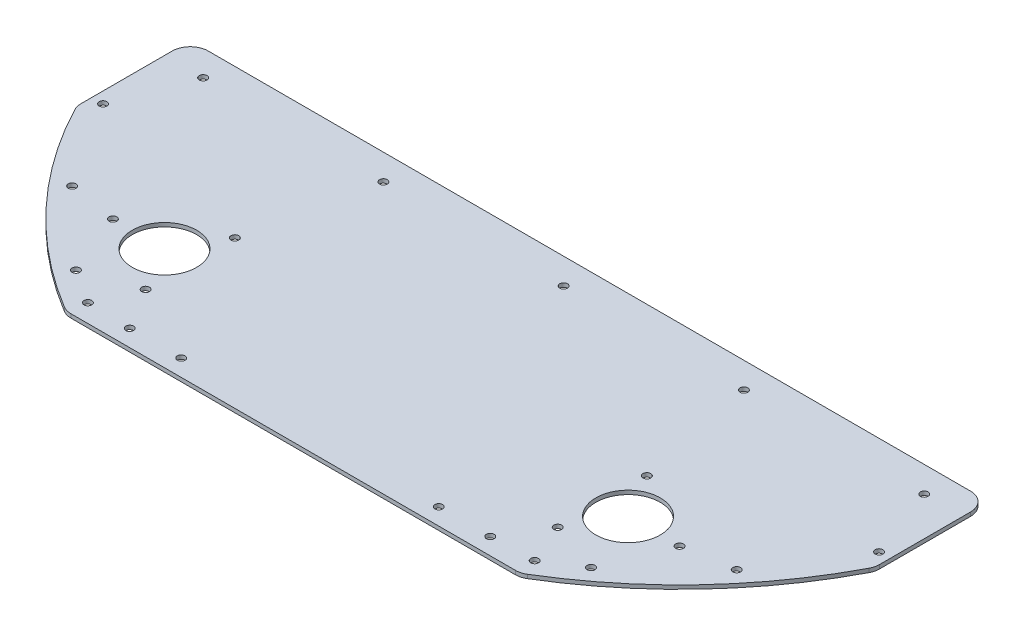
SolidWorks part; units mm, degrees
material "3.3535 (EN-AW 5754)"
ref_plane "Plan de face" through (0, 0, 0) normal (0, 0, 1) x (1, 0, 0)
ref_plane "Plan de dessus" through (0, 0, 0) normal (0, 1, 0) x (1, 0, 0)
ref_plane "Plan de droite" through (0, 0, 0) normal (1, 0, 0) x (0, 0, -1)
sketch "Esquisse1" plane through (0, 0, 0) normal (0, 1, 0) x (1, 0, 0)
  line L0 (0, 0) -> (0, -150) construction
  line L1 (-155, -35) -> (155, -35)
  line L2 (-155, -35) -> (-155, -79.0633)
  line L3 (-88.1816, -150) -> (88.1816, -150)
  line L6 (155, -35) -> (155, -79.0633)
  line L8 (110, -110) -> (90, -110) construction
  circle A0 centre (-70, -45) radius 1.5
  circle A1 centre (0, -45) radius 1.5
  circle A2 centre (90, -110) radius 12.5
  circle A3 centre (80, -127.3205) radius 1.5
  circle A4 centre (110, -110) radius 1.5
  circle A5 centre (80, -92.6795) radius 1.5
  circle A6 centre (90, -110) radius 20 construction
  circle A7 centre (70, -45) radius 1.5
  circle A8 centre (-140, -45) radius 1.5
  circle A9 centre (140, -45) radius 1.5
  arc A10 (-155, -79.0633) -> (-88.1816, -150) centre (0, 0) ccw
  arc A11 (88.1816, -150) -> (155, -79.0633) centre (0, 0) ccw
  circle A12 centre (-86.7385, -143) radius 1.5
  circle A13 centre (86.7385, -143) radius 1.5
  circle A14 centre (-80, -92.6795) radius 1.5
  circle A15 centre (-80, -127.3205) radius 1.5
  circle A16 centre (-90, -110) radius 12.5
  circle A17 centre (-110, -110) radius 1.5
  circle A18 centre (0, 0) radius 167.25 construction
  dimension "D2" = 70
  dimension "D3" = 10
  dimension "D4" = 3
  dimension "D5" = 45
  dimension "D7" = 120
  dimension "D8" = 40
  dimension "D10" = 3
  dimension "D11" = 25
  dimension "D12" = 310
  dimension "D15" = 70
  dimension "D16" = 334.5
  dimension "D18" = 3
  dimension "D19" = 6.75
  dimension "D20" = 90
  dimension "D21" = 40
  dimension "D13" = 348
  dimension "D17" = 7
  dimension "D6" = 150
  dimension "D9" = 120
  dimension "D14" = 173.4769
extrude "Boss.-Extru.1" add sketch "Esquisse1" along normal blind 1.5
fillet "Congé1" radius 7 6 edges at (-155, 0.75, 35) (155, 0.75, 35) (155, 0.75, 79.0633) (88.1816, 0.75, 150) (-155, 0.75, 79.0633) (-88.1816, 0.75, 150)
hole_wizard "Diamètre du perçage Ø3.0 (3)1" positions "Esquisse2" profile "Esquisse3" hole size "Ø3.0" standard "Ansi Metric" end condition through all
sketch "Esquisse2" plane through (0, 1.5, 0) normal (0, 1, 0) x (1, 0, 0)
  line L0 (-150.6593, -73.1985) -> (-129.0082, -106.8322) construction
  line L1 (-129.0082, -106.8322) -> (-100, -134.3735) construction
  line L4 (-86.2554, -150) -> (86.2554, -150) construction
  line L5 (0, -0.825) -> (0, 0.825) construction
  circle A0 centre (0, 0) radius 167.5 construction
  arc A1 (-154.2036, -80.6055) -> (-89.8709, -148.994) centre (0, 0) ccw construction
  point P0 (-150.6593, -73.1985)
  point P2 (-129.0082, -106.8322)
  point P4 (-100, -134.3735)
  point P6 (-70, -143.5)
  point P8 (-50, -143.5)
  point P36 (70, -143.5)
  point P37 (100, -134.3735)
  point P38 (129.0082, -106.8322)
  point P39 (150.6593, -73.1985)
  point P43 (50, -143.5)
  dimension "D1" = 6.5
  dimension "D2" = 335
  dimension "D3" = 100
  dimension "D4" = 40
  dimension "D5" = 20
  dimension "D6" = 6.5
  dimension "D7" = 140
  dimension "D8" = 100
sketch "Esquisse3" plane through (-150.6593, 1.5, 73.1985) normal (1, 0, 0) x (0, 0, 1)
  line L0 (0, 0) -> (0, 1.5)
  line L1 (0, 1.5) -> (1.5, 1.5)
  line L2 (1.5, 1.5) -> (1.5, 0)
  line L5 (1.5, 0) -> (0, 0)
  line L11 (0, -6.35) -> (0, 107.95) construction
  dimension "Diamètre du perçage jusqu'au prochain" = 3
  dimension "Profondeur du perçage jusqu'au prochain" = 1.5
